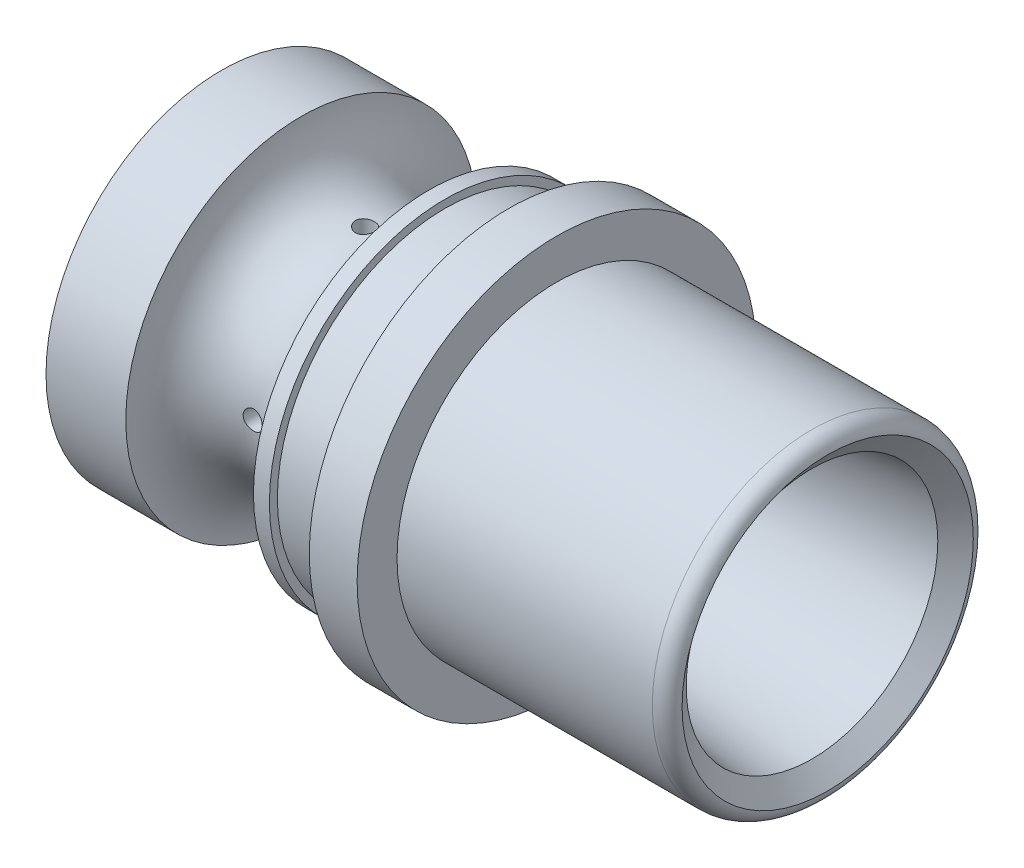
SolidWorks part; units mm, degrees
ref_plane "Спереди" through (0, 0, 0) normal (0, 0, 1) x (1, 0, 0)
ref_plane "Сверху" through (0, 0, 0) normal (0, 1, 0) x (1, 0, 0)
ref_plane "Справа" through (0, 0, 0) normal (1, 0, 0) x (0, 0, -1)
sketch "Эскиз1" plane through (0, 0, 0) normal (0, 0, 1) x (1, 0, 0)
  line L0 (0, 0) -> (0, 5.5)
  line L1 (0, 5.5) -> (7, 5.5)
  line L2 (7, 5.5) -> (7, 5.25)
  line L3 (7, 5.25) -> (9, 5.25)
  line L4 (9, 5.25) -> (9, 6.25)
  line L5 (9, 6.25) -> (10.5, 6.25)
  line L6 (10.5, 6.25) -> (10.5, 5)
  line L7 (10.5, 5) -> (19, 5)
  line L8 (19, 5) -> (19, 0)
  line L9 (19, 0) -> (0, 0)
  line L10 (-6.6467, 0) -> (28.5279, 0) construction
  dimension "D1" = 5.5
  dimension "D2" = 19
  dimension "D3" = 5
  dimension "D4" = 7
  dimension "D5" = 1.5
  dimension "D6" = 5.25
  dimension "D7" = 6.25
  dimension "D8" = 9
revolve "Повернуть31" add sketch "Эскиз1" angle 360 about L10
sketch "Эскиз2" plane through (0, 0, 0) normal (0, 0, 1) x (1, 0, 0)
  line L0 (0, 0) -> (19, 0)
  line L1 (0, 5.5) -> (0, -5.5) construction
  line L2 (19, -5) -> (19, 5) construction
  line L3 (19, 0) -> (19, 4)
  line L4 (19, 4) -> (6.3206, 2.5554)
  line L5 (6.3206, 2.5554) -> (6, 2)
  line L6 (6, 2) -> (4, 2)
  line L7 (0, 0) -> (0, 5)
  line L8 (0, 0) -> (22.6338, 0) construction
  arc A0 (4, 2) -> (0, 5) centre (-0.5981, 0.0359) ccw
  dimension "D6" = 5
  dimension "D1" = 4
  dimension "D2" = 13
  dimension "D3" = 5
  dimension "D4" = 2
  dimension "D5" = 4
  dimension "D7" = 120
  dimension "D8" = 6.5
revolve "Вырез-Повернуть2" cut sketch "Эскиз2" angle 360 about L8
sketch "Эскиз4" plane through (0, 0, 0) normal (0, 0, 1) x (1, 0, 0)
  line L0 (0, 0) -> (18.9957, 0) construction
  line L2 (7, 5.5) -> (0, 5.5) construction
  circle A1 centre (4.5, 5.5) radius 2
  dimension "D1" = 4
  dimension "D2" = 4.5
revolve "Вырез-Повернуть3" cut sketch "Эскиз4" angle 360 about L0
sketch "Эскиз5" plane through (0, 0, 0) normal (0, 0, 1) x (1, 0, 0)
  line L0 (0, 0) -> (9, 0) construction
  circle A0 centre (4.5, 0) radius 0.3
  dimension "D2" = 0.6
  dimension "D1" = 4.5
extrude "Вырез-Вытянуть1" cut sketch "Эскиз5" against normal through all and the other way through all
pattern_circular "Круговой массив6" count 2 every 90 about axis through (-6.6467, 0, 0) along (-1, 0, 0) of "Вырез-Вытянуть1" reverse direction yes
fillet "Скругление1" radius 0.5 1 edges at (19, 0, 5)
chamfer "Фаска1" distance 0.5 angle 45 1 edges at (19, 0, 4) first distance on face at (6.3206, 0, 2.5554)
fillet "Скругление2" radius 0.5 1 edges at (6.3206, 0, 2.5554)
